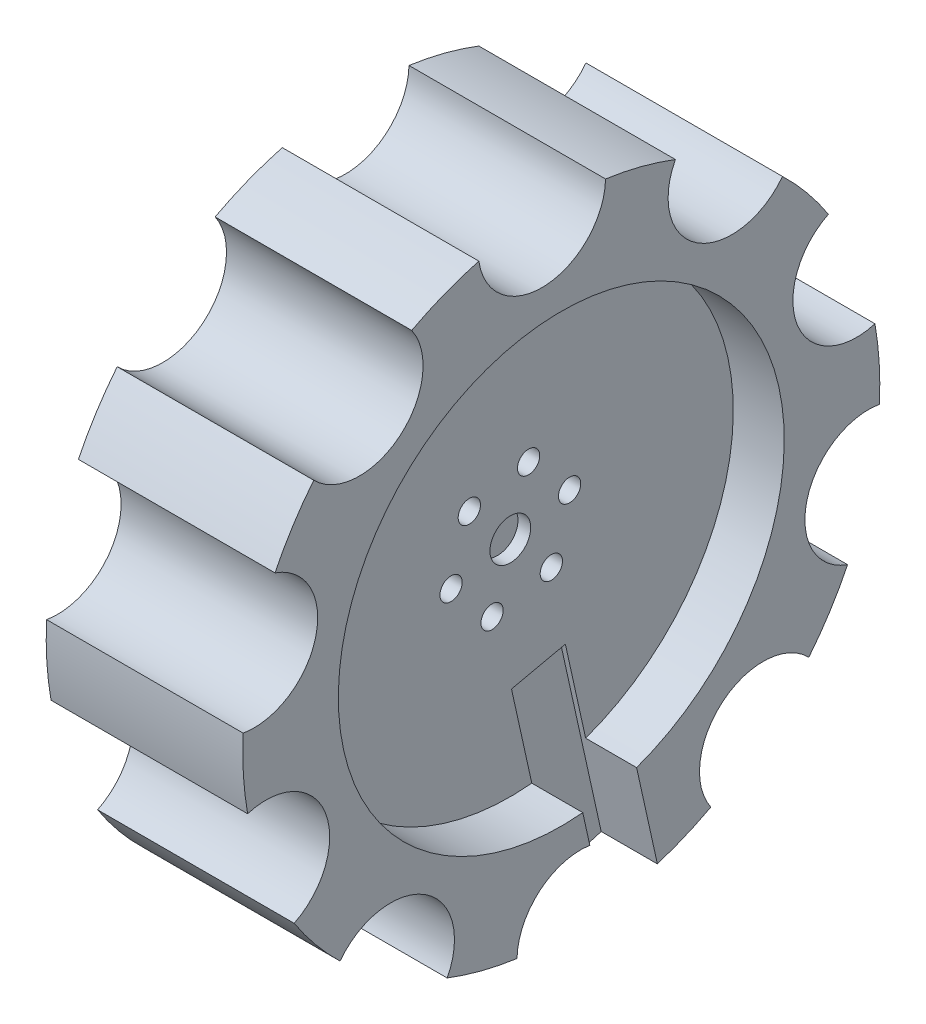
SolidWorks part; units mm, degrees
ref_plane "Front Plane" through (0, 0, 0) normal (0, 0, 1) x (1, 0, 0)
ref_plane "Top Plane" through (0, 0, 0) normal (0, 1, 0) x (1, 0, 0)
ref_plane "Right Plane" through (0, 0, 0) normal (1, 0, 0) x (0, 0, -1)
sketch "Sketch1" plane through (0, 0, 0) normal (1, 0, 0) x (0, 0, -1)
  circle A0 centre (0, 0) radius 50
extrude "Boss-Extrude1" add sketch "Sketch1" along normal blind 30.86
ref_axis "WheelAxis" through (0, 0, 0) along (1, 0, 0)
ref_point "Point1"
ref_point "Point2"
sketch "Sketch2" plane through (30.86, 0, 0) normal (1, 0, 0) x (0, 0, -1)
  circle A0 centre (0, 0) radius 35
extrude "Cut-Extrude1" cut sketch "Sketch2" against normal blind 8
sketch "Sketch3" plane through (0, 0, 0) normal (-1, 0, 0) x (0, 0, 1)
  circle A0 centre (0, 0) radius 29.8357
sketch "Sketch5" plane through (0, 0, 0) normal (-1, 0, 0) x (0, 0, 1)
  line L1 (-2.8683, 9.0881) -> (-9.3047, 2.0601) construction
  line L2 (-9.3047, 2.0601) -> (-6.4364, -7.0281) construction
  line L3 (-6.4364, -7.0281) -> (2.8683, -9.0881) construction
  line L4 (2.8683, -9.0881) -> (9.3047, -2.0601) construction
  line L5 (9.3047, -2.0601) -> (6.4364, 7.0281) construction
  line L6 (6.4364, 7.0281) -> (-2.8683, 9.0881) construction
  circle A0 centre (0, 0) radius 9.53 construction
  circle A1 centre (0, 0) radius 8.2532 construction
  circle A2 centre (2.8683, -9.0881) radius 1.75
  circle A3 centre (-6.4364, -7.0281) radius 1.75
  circle A4 centre (-9.3047, 2.0601) radius 1.75
  circle A5 centre (-2.8683, 9.0881) radius 1.75
  circle A6 centre (6.4364, 7.0281) radius 1.75
  circle A7 centre (9.3047, -2.0601) radius 1.75
ref_axis "ReferenceAxisForOrientation" through (0, -2.0601, 9.3047) along (0, 0.2162, -0.9764)
ref_plane "Plane1" through (0, 0, 0) normal (0, 0.9764, 0.2162) x (1, 0, 0)
sketch "Sketch10" plane through (0, 0, 0) normal (0, 0.9764, 0.2162) x (1, 0, 0)
  line L1 (22.0394, 4.422) -> (32.0581, 4.422)
  line L2 (22.0394, 4.422) -> (22.0394, -4.2399)
  line L3 (22.0394, -4.2399) -> (32.0581, -4.2399)
  line L4 (32.0581, 4.422) -> (32.0581, -4.2399)
extrude "Cut-Extrude4" cut sketch "Sketch10" against normal blind 60 from offset 20 offset against normal yes
ref_point "Point5"
sketch "Sketch12" plane through (22.86, 0, 0) normal (1, 0, 0) x (0, 0, -1)
  circle A0 centre (0, 0) radius 3.2
extrude "Cut-Extrude5" cut sketch "Sketch12" against normal blind 2
extrude "Cut-Extrude3" cut sketch "Sketch5" against normal blind 30
sketch "Sketch8" plane through (0, 0, 0) normal (-1, 0, 0) x (0, 0, 1)
  circle A0 centre (-2.8683, 9.0881) radius 4
  circle A1 centre (6.4364, 7.0281) radius 4
  circle A2 centre (9.3047, -2.0601) radius 4
  circle A3 centre (2.8683, -9.0881) radius 4
  circle A4 centre (-6.4364, -7.0281) radius 4
  circle A5 centre (-9.3047, 2.0601) radius 4
extrude "Cut-Extrude6" cut sketch "Sketch8" against normal blind 10
sketch "Sketch13" plane through (0, 0, 0) normal (-1, 0, 0) x (0, 0, 1)
  line L1 (-48.2406, -12.4708) -> (-31.6973, -38.4442) construction
  line L2 (-31.6973, -38.4442) -> (-3.0467, -49.7332) construction
  line L3 (-3.0467, -49.7332) -> (26.7676, -42.0258) construction
  line L4 (26.7676, -42.0258) -> (46.3576, -18.266) construction
  line L5 (46.3576, -18.266) -> (48.2406, 12.4708) construction
  line L6 (48.2406, 12.4708) -> (31.6973, 38.4442) construction
  line L7 (31.6973, 38.4442) -> (3.0467, 49.7332) construction
  line L8 (3.0467, 49.7332) -> (-26.7676, 42.0258) construction
  line L9 (-26.7676, 42.0258) -> (-46.3576, 18.266) construction
  line L10 (-46.3576, 18.266) -> (-48.2406, -12.4708) construction
  circle A0 centre (0, 0) radius 47.3878 construction
  circle A1 centre (48.2406, 12.4708) radius 10
  circle A2 centre (46.3576, -18.266) radius 10
  circle A3 centre (26.7676, -42.0258) radius 10
  circle A4 centre (-3.0467, -49.7332) radius 10
  circle A5 centre (-31.6973, -38.4442) radius 10
  circle A6 centre (-48.2406, -12.4708) radius 10
  circle A7 centre (-46.3576, 18.266) radius 10
  circle A8 centre (-26.7676, 42.0258) radius 10
  circle A9 centre (3.0467, 49.7332) radius 10
  circle A10 centre (31.6973, 38.4442) radius 10
extrude "Cut-Extrude8" cut sketch "Sketch13" against normal blind 40
